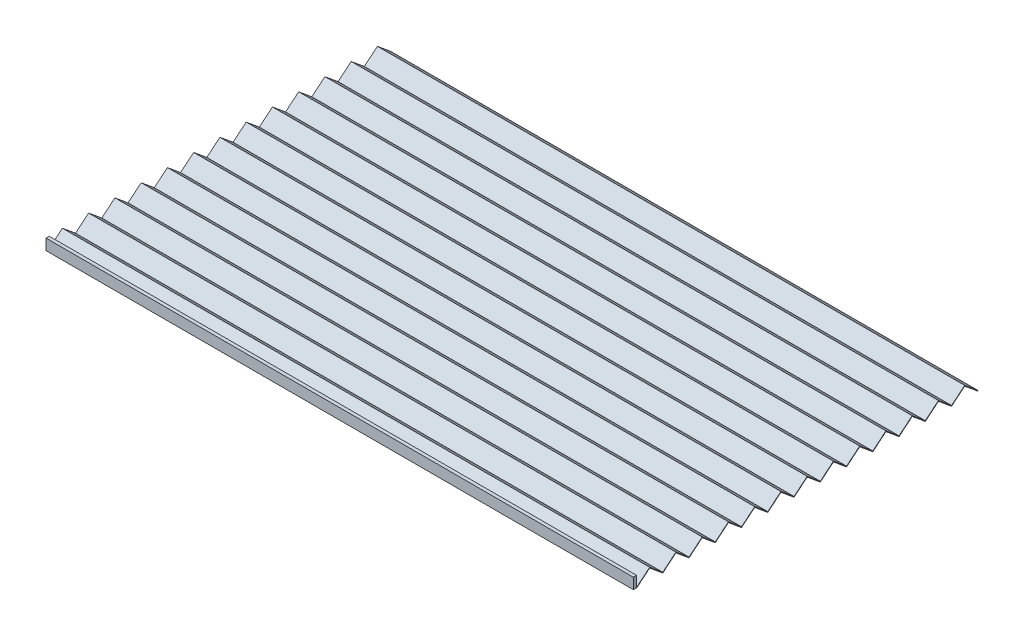
SolidWorks part; units mm, degrees
ref_plane "Front Plane" through (0, 0, 0) normal (0, 0, 1) x (1, 0, 0)
ref_plane "Top Plane" through (0, 0, 0) normal (0, 1, 0) x (1, 0, 0)
ref_plane "Right Plane" through (0, 0, 0) normal (1, 0, 0) x (0, 0, -1)
sketch "Sketch2" plane through (0, 0, 0) normal (0, 0, 1) x (1, 0, 0)
  line L1 (-270, 10) -> (270, 10)
  line L2 (-270, 10) -> (-270, 0)
  line L3 (-270, 0) -> (270, 0)
  line L4 (270, 10) -> (270, 0)
  point P4 (0, 0)
  dimension "D1" = 10
  dimension "D2" = 540
extrude "Boss-Extrude1" add sketch "Sketch2" along normal blind 3
sketch "Sketch3" plane through (270, 0, 0) normal (1, 0, 0) x (0, 0, -1)
  line L0 (0, 10) -> (313.8174, 10) construction
  line L1 (0, 0) -> (313.8174, 0) construction
  line L2 (313.8174, 10) -> (313.8174, 0) construction
  line L3 (0, 0) -> (12.0699, 10)
  line L4 (12.0699, 10) -> (24.1398, 0)
  line L5 (24.1398, 0) -> (36.2097, 10)
  line L6 (36.2097, 10) -> (48.2796, 0)
  line L7 (48.2796, 0) -> (60.3495, 10)
  line L8 (60.3495, 10) -> (72.4194, 0)
  line L9 (72.4194, 0) -> (84.4893, 10)
  line L10 (84.4893, 10) -> (96.5592, 0)
  line L11 (96.5592, 0) -> (108.6291, 10)
  line L12 (108.6291, 10) -> (120.699, 0)
  line L13 (120.699, 0) -> (132.7689, 10)
  line L14 (132.7689, 10) -> (144.8388, 0)
  line L15 (144.8388, 0) -> (156.9087, 10)
  line L16 (156.9087, 10) -> (168.9786, 0)
  line L17 (168.9786, 0) -> (181.0485, 10)
  line L18 (181.0485, 10) -> (193.1184, 0)
  line L20 (193.1184, 0) -> (205.1883, 10)
  line L21 (205.1883, 10) -> (217.2582, 0)
  line L22 (217.2582, 0) -> (229.3281, 10)
  line L23 (229.3281, 10) -> (241.398, 0)
  line L24 (241.398, 0) -> (253.4679, 10)
  line L25 (253.4679, 10) -> (265.5378, 0)
  line L26 (265.5378, 0) -> (277.6077, 10)
  line L27 (277.6077, 10) -> (289.6776, 0)
  line L28 (289.6776, 0) -> (301.7475, 10)
  line L29 (301.7475, 10) -> (313.8174, 0)
  line L30 (313.8174, 10) -> (313.8174, 0) construction
extrude "Extrude-Thin1" add sketch "Sketch3" against normal through all thin thin type mid plane wall 0.5
